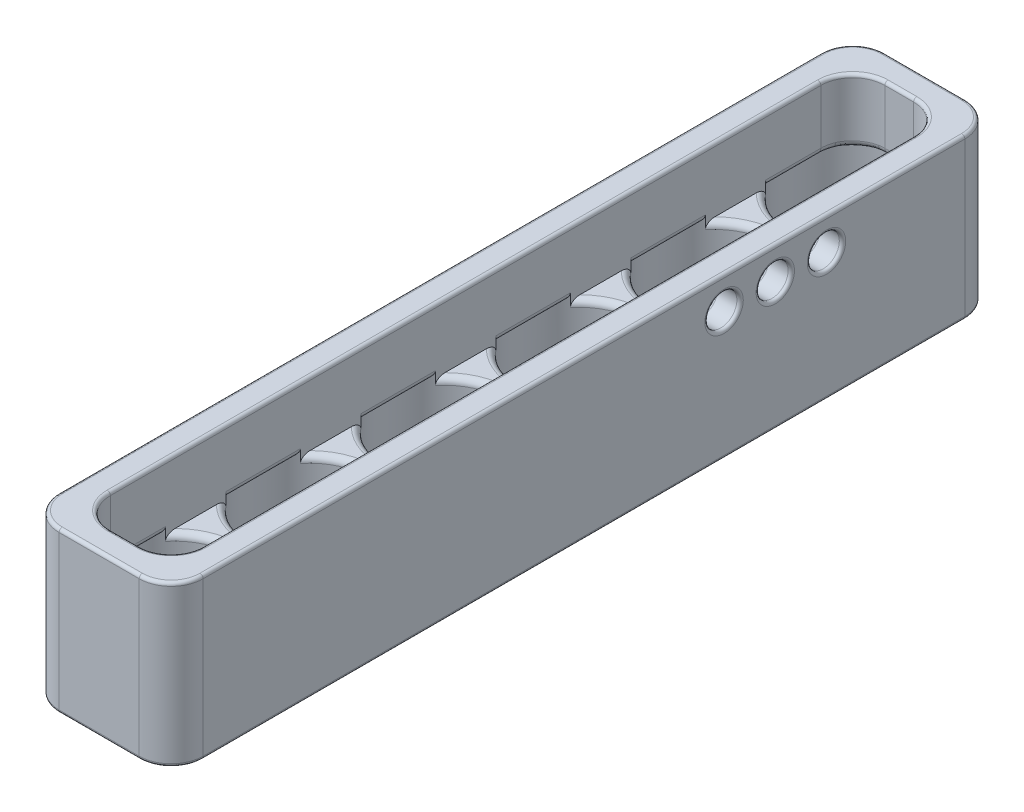
SolidWorks part; units mm, degrees
ref_plane "Front Plane" through (0, 0, 0) normal (0, 0, 1) x (1, 0, 0)
ref_plane "Top Plane" through (0, 0, 0) normal (0, 1, 0) x (1, 0, 0)
ref_plane "Right Plane" through (0, 0, 0) normal (1, 0, 0) x (0, 0, -1)
sketch "Esquisse1" plane through (0, 0, 0) normal (0, 1, 0) x (1, 0, 0)
  line L0 (0, 64.5) -> (0, -64.5) construction
  line L1 (-11.25, 64.5) -> (11.25, 64.5)
  line L2 (-11.25, 64.5) -> (-11.25, -64.5)
  line L3 (-11.25, -64.5) -> (11.25, -64.5)
  line L4 (11.25, 64.5) -> (11.25, -64.5)
  line L5 (-11.25, 64.5) -> (11.25, -64.5) construction
  line L6 (-11.25, -64.5) -> (11.25, 64.5) construction
  line L7 (0, -1.242) -> (0, 0) construction
  circle A0 centre (0, -10.542) radius 9.3
  circle A1 centre (0, -31.6277) radius 9.3
  circle A2 centre (0, -52.7134) radius 9.3
  circle A3 centre (0, -10.542) radius 9.3
  circle A4 centre (0, -31.6277) radius 9.3
  circle A5 centre (0, 10.5437) radius 9.3
  circle A6 centre (0, -10.542) radius 9.3
  circle A7 centre (0, 31.6294) radius 9.3
  circle A8 centre (0, 10.5437) radius 9.3
  circle A9 centre (0, 10.5437) radius 9.3
  circle A10 centre (0, 31.6294) radius 9.3
  circle A11 centre (0, 52.7151) radius 9.3
  point P0 (0, 0)
  dimension "D3" = 18.6
  dimension "D1" = 129
  dimension "D2" = 22.5
  dimension "D4" = 1.242
  dimension "D5" = 3
  dimension "D6" = 4
extrude "Boss.-Extru.1" add sketch "Esquisse1" along normal blind 25 contours L4 L1 L2 L3 A11 A7 A5 A2 A1 A0 region at (0, 0, 0.0011)
sketch "Esquisse2" plane through (0, 0, 64.5) normal (0, 0, 1) x (1, 0, 0)
  line L0 (-11.25, 25) -> (11.25, 25) construction
  line L1 (-7.25, 25) -> (7.25, 25)
  line L2 (-7.25, 25) -> (-7.25, 15)
  line L3 (-7.25, 15) -> (7.25, 15)
  line L4 (7.25, 25) -> (7.25, 15)
  line L5 (-11.25, 25) -> (-11.25, 0) construction
  line L6 (11.25, 25) -> (11.25, 0) construction
  dimension "D1" = 4
  dimension "D2" = 4
  dimension "D3" = 10
extrude "Enlèv. mat.-Extru.1" cut sketch "Esquisse2" against normal through all both and the other way through all
sketch "Esquisse3" plane through (0, 25, 0) normal (0, 1, 0) x (1, 0, 0)
  line L1 (11.25, 64.5) -> (7.25, 64.5)
  line L2 (11.25, 64.5) -> (11.25, -64.5)
  line L3 (11.25, -64.5) -> (7.25, -64.5)
  line L4 (7.25, 64.5) -> (7.25, -64.5)
  line L5 (-7.25, -64.5) -> (-11.25, -64.5)
  line L6 (-7.25, -64.5) -> (-7.25, 64.5)
  line L7 (-7.25, 64.5) -> (-11.25, 64.5)
  line L8 (-11.25, -64.5) -> (-11.25, 64.5)
extrude "Boss.-Extru.2" add sketch "Esquisse3" against normal up to surface (10 mm away) up to face at (0, 15, 62.3879)
sketch "Esquisse4" plane through (0, 25, 0) normal (0, 1, 0) x (1, 0, 0)
  line L0 (11.25, 64.5) -> (11.25, -64.5) construction
  line L1 (-11.25, 64.5) -> (11.25, 64.5)
  line L2 (-11.25, 64.5) -> (-11.25, 60.5)
  line L3 (-11.25, 60.5) -> (11.25, 60.5)
  line L4 (11.25, 64.5) -> (11.25, 60.5)
  line L6 (-11.25, -64.5) -> (11.25, -64.5)
  line L7 (-11.25, -64.5) -> (-11.25, -60.5)
  line L8 (-11.25, -60.5) -> (11.25, -60.5)
  line L9 (11.25, -64.5) -> (11.25, -60.5)
  dimension "D1" = 4
  dimension "D2" = 4
extrude "Boss.-Extru.3" add sketch "Esquisse4" against normal up to surface (10 mm away) up to face at (0, 15, -62.3887)
fillet "Congé1" radius 5 4 edges at (-7.25, 20, 60.5) (7.25, 20, 60.5) (-7.25, 20, -60.5) (7.25, 20, -60.5)
fillet "Congé2" radius 5 4 edges at (-11.25, 12.5, -64.5) (11.25, 12.5, -64.5) (11.25, 12.5, 64.5) (-11.25, 12.5, 64.5)
fillet "Congé3" radius 0.5 30 edges at (-5.7855, 25, -59.0355) (0, 25, -60.5) (5.7855, 25, -59.0355) (7.25, 25, 0) (5.7855, 25, 59.0355) (0, 25, 60.5) (-5.7855, 25, 59.0355) (9.7855, 25, -63.0355) (0, 25, -64.5) (-9.7855, 25, -63.0355) (-11.25, 25, 0) (-9.7855, 25, 63.0355) (0, 25, 64.5) (9.7855, 25, 63.0355) (9.7855, 0, -63.0355) (0, 0, -64.5) (-9.7855, 0, -63.0355) (-11.25, 0, 0) (-9.7855, 0, 63.0355) (0, 0, 64.5) (9.7855, 0, 63.0355) (-7.25, 25, 0) (11.25, 25, 0) (0, 0, 62.0134) (0, 0, 40.9277) (0, 0, 19.842) (0, 0, -1.2437) (0, 0, -22.3294) (0, 0, -43.4151) (11.25, 0, 0)
sketch "Esquisse5" plane through (11.25, 0, 0) normal (1, 0, 0) x (0, 0, -1)
  line L6 (18.9829, 20) -> (38.9829, 20) construction
  line L7 (-59.5, 25) -> (59.5, 25) construction
  circle A0 centre (29.8873, 20) radius 2.5
  circle A1 centre (37.8873, 20) radius 2.5
  circle A2 centre (21.8873, 20) radius 2.5
  dimension "D3" = 5
  dimension "D4" = 5
  dimension "D7" = 5
  dimension "D1" = 20
  dimension "D2" = 5
  dimension "D5" = 8
  dimension "D6" = 8
extrude "Enlèv. mat.-Extru.2" cut sketch "Esquisse5" against normal blind 12 and the other way through all
fillet "Congé5" radius 0.5 6 edges at (7.25, 22.5, -37.8873) (7.25, 22.5, -29.8873) (7.25, 22.5, -21.8873) (11.25, 20, -40.3873) (11.25, 20, -32.3873) (11.25, 20, -24.3873)
fillet "Congé6" radius 1 16 edges at (7.25, 15, 51.1943) (5.7855, 15, 59.0355) (0, 15, 60.5) (-5.7855, 15, 59.0355) (-7.25, 15, -51.1952) (-5.7855, 15, -59.0355) (0, 15, -60.5) (5.7855, 15, -59.0355) (7.25, 15, -31.6294) (7.25, 15, -10.5437) (7.25, 15, 10.542) (7.25, 15, 31.6277) (-7.25, 15, 31.6277) (-7.25, 15, 10.542) (-7.25, 15, -10.5437) (-7.25, 15, -31.6294)
fillet "Congé7" radius 1 10 edges at (0, 15, 43.4134) (0, 15, 40.9277) (0, 15, 22.3277) (0, 15, 19.842) (0, 15, 1.242) (0, 15, -1.2437) (0, 15, -19.8437) (0, 15, -22.3294) (0, 15, -40.9294) (0, 15, -43.4151)
sketch "Esquisse6" plane through (0, 15, 0) normal (0, 1, 0) x (1, 0, 0)
  line L0 (7.25, -42.1705) -> (5.65, -42.1705) construction
  line L1 (7.25, -38.9439) -> (7.25, -45.3972) construction
  circle A0 centre (5.65, -42.1705) radius 1.5019
  dimension "D1" = 1.6
extrude "Enlèv. mat.-Extru.3" cut sketch "Esquisse6" against normal through all
